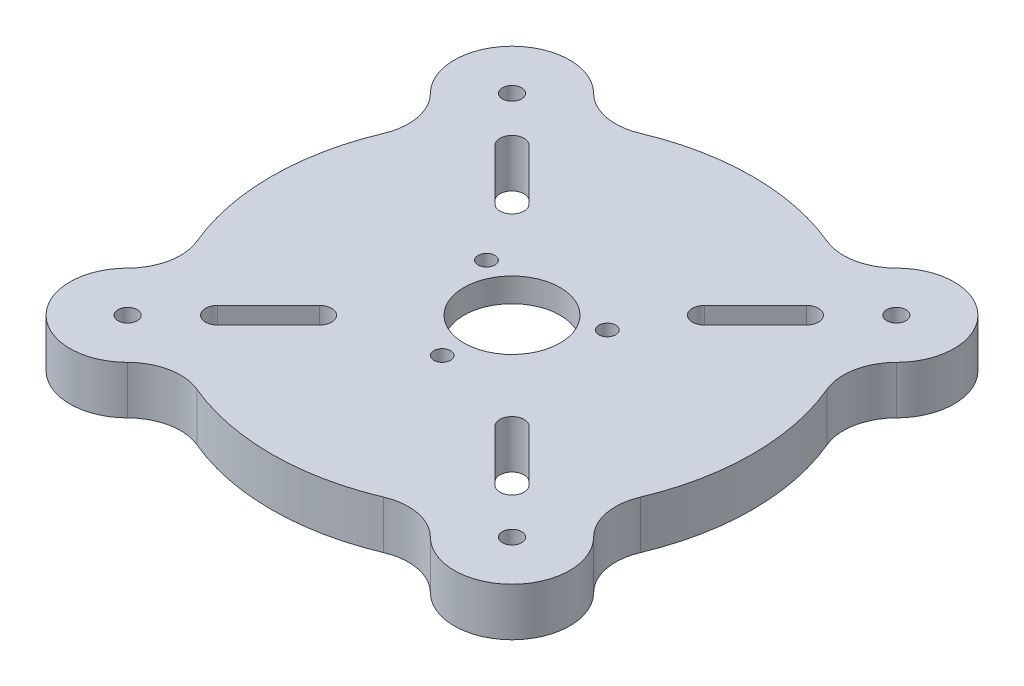
SolidWorks part; units mm, degrees
ref_plane "Front Plane" through (0, 0, 0) normal (0, 0, 1) x (1, 0, 0)
ref_plane "Top Plane" through (0, 0, 0) normal (0, 1, 0) x (1, 0, 0)
ref_plane "Right Plane" through (0, 0, 0) normal (1, 0, 0) x (0, 0, -1)
sketch "Sketch2" plane through (0, 0, 0) normal (0, 1, 0) x (1, 0, 0)
  line L0 (-39.9515, -39.9515) -> (39.9515, 39.9515) construction
  line L1 (-48.4368, -31.4663) -> (31.4663, 48.4368) construction
  line L2 (-31.4663, -48.4368) -> (48.4368, 31.4663) construction
  line L3 (0, 0) -> (0, 50) construction
  line L4 (39.9515, -39.9515) -> (-39.9515, 39.9515) construction
  line L5 (48.4368, -31.4663) -> (-31.4663, 48.4368) construction
  line L6 (31.4663, -48.4368) -> (-48.4368, 31.4663) construction
  line L7 (20, 20) -> (30.6066, 30.6066) construction
  line L8 (18.2322, 21.7678) -> (28.8388, 32.3744)
  line L9 (21.7678, 18.2322) -> (32.3744, 28.8388)
  line L10 (20, -20) -> (30.6066, -30.6066) construction
  line L11 (21.7678, -18.2322) -> (32.3744, -28.8388)
  line L12 (18.2322, -21.7678) -> (28.8388, -32.3744)
  line L13 (-20, -20) -> (-30.6066, -30.6066) construction
  line L14 (-18.2322, -21.7678) -> (-28.8388, -32.3744)
  line L15 (-21.7678, -18.2322) -> (-32.3744, -28.8388)
  line L16 (-20, 20) -> (-30.6066, 30.6066) construction
  line L17 (-21.7678, 18.2322) -> (-32.3744, 28.8388)
  line L18 (-18.2322, 21.7678) -> (-28.8388, 32.3744)
  circle A0 centre (0, 0) radius 50
  arc A1 (-48.4368, -31.4663) -> (-31.4663, -48.4368) centre (-39.9515, -39.9515) ccw construction
  arc A2 (48.4368, 31.4663) -> (31.4663, 48.4368) centre (39.9515, 39.9515) ccw construction
  arc A3 (48.4368, -31.4663) -> (31.4663, -48.4368) centre (39.9515, -39.9515) cw construction
  arc A4 (-48.4368, 31.4663) -> (-31.4663, 48.4368) centre (-39.9515, 39.9515) cw construction
  arc A5 (19.4135, 46.0773) -> (31.4663, 48.4368) centre (23.6858, 56.2173) ccw
  arc A6 (48.4368, 31.4663) -> (46.0773, 19.4135) centre (56.2173, 23.6858) ccw
  arc A7 (18.2322, 21.7678) -> (21.7678, 18.2322) centre (20, 20) ccw
  arc A8 (32.3744, 28.8388) -> (28.8388, 32.3744) centre (30.6066, 30.6066) ccw
  circle A9 centre (39.9515, 39.9515) radius 2
  arc A10 (31.4663, 48.4368) -> (48.4368, 31.4663) centre (39.9515, 39.9515) cw
  arc A11 (46.0773, -19.4135) -> (48.4368, -31.4663) centre (56.2173, -23.6858) ccw
  arc A12 (48.4368, -31.4663) -> (31.4663, -48.4368) centre (39.9515, -39.9515) cw
  arc A13 (31.4663, -48.4368) -> (19.4135, -46.0773) centre (23.6858, -56.2173) ccw
  arc A14 (-19.4135, -46.0773) -> (-31.4663, -48.4368) centre (-23.6858, -56.2173) ccw
  arc A15 (-31.4663, -48.4368) -> (-48.4368, -31.4663) centre (-39.9515, -39.9515) cw
  arc A16 (-48.4368, -31.4663) -> (-46.0773, -19.4135) centre (-56.2173, -23.6858) ccw
  arc A17 (-46.0773, 19.4135) -> (-48.4368, 31.4663) centre (-56.2173, 23.6858) ccw
  arc A18 (-48.4368, 31.4663) -> (-31.4663, 48.4368) centre (-39.9515, 39.9515) cw
  arc A19 (-31.4663, 48.4368) -> (-19.4135, 46.0773) centre (-23.6858, 56.2173) ccw
  circle A20 centre (39.9515, -39.9515) radius 2
  arc A21 (21.7678, -18.2322) -> (18.2322, -21.7678) centre (20, -20) ccw
  arc A22 (28.8388, -32.3744) -> (32.3744, -28.8388) centre (30.6066, -30.6066) ccw
  circle A23 centre (-39.9515, -39.9515) radius 2
  arc A24 (-18.2322, -21.7678) -> (-21.7678, -18.2322) centre (-20, -20) ccw
  arc A25 (-32.3744, -28.8388) -> (-28.8388, -32.3744) centre (-30.6066, -30.6066) ccw
  circle A26 centre (-39.9515, 39.9515) radius 2
  arc A27 (-21.7678, 18.2322) -> (-18.2322, 21.7678) centre (-20, 20) ccw
  arc A28 (-28.8388, 32.3744) -> (-32.3744, 28.8388) centre (-30.6066, 30.6066) ccw
  point P5 (0, 0)
  point P13 (0, 0)
  point P26 (25.3033, 25.3033)
  point P59 (0, 0)
  point P63 (25.3033, -25.3033)
  point P72 (-25.3033, -25.3033)
  point P81 (-25.3033, 25.3033)
  point P88 (0, 0)
  dimension "D1" = 100
  dimension "D2" = 12
  dimension "D5" = 2.5
  dimension "D8" = 4
  dimension "D3" = 113
  dimension "D4" = 45
  dimension "D6" = 15
  dimension "D7" = 20
  dimension "D11" = 18.2322
  dimension "D12" = 19.4135
  dimension "D13" = 18.2322
  dimension "D14" = 19.4135
  dimension "D9" = 4
  dimension "D10" = 4
extrude "Boss-Extrude2" add sketch "Sketch2" along normal blind 10 contours A19 A18 A17 A0 A26 | A16 A15 A14 A0 A23 | A0 A28 L18 A27 L17 A25 L15 A24 L14 A22 L12 A21 L11 A8 L9 A7 L8 | A13 A12 A11 A0 A20 | A10 A5 A0 A6 A9 region at (0, 0, 0) region at (35.6807, 0, -35.6807) region at (44.9674, 0, 25.8881) region at (-35.6807, 0, -35.6807) region at (-25.8881, 0, 44.9674)
sketch "Sketch3" plane through (0, 0, 0) normal (0, -1, 0) x (1, 0, 0)
  circle A0 centre (0, 0) radius 21.25
  circle A1 centre (0, 14.5) radius 1.75
  circle A2 centre (12.5574, -7.25) radius 1.75
  circle A3 centre (-12.5574, -7.25) radius 1.75
  point P12 (0, 0)
  dimension "D1" = 42.5
  dimension "D2" = 3.5
  dimension "D3" = 14.5
  dimension "D5" = 35.8794
  dimension "D6" = 48.4368
  dimension "D7" = 60.9942
  dimension "D4" = 3
extrude "Cut-Extrude8" cut sketch "Sketch3" against normal blind 5 contours A0 A3 A2 A1 region at (0, 0, 0)
extrude "Cut-Extrude9" cut sketch "Sketch3<9>" against normal through all contours A3 | A1 | A2
sketch "Sketch3<9>" plane through (0, 0, 0) normal (0, -1, 0) x (1, 0, 0) same geometry as "Sketch3"
sketch "Sketch5" plane through (0, 5, 0) normal (0, -1, 0) x (1, 0, 0)
  circle A0 centre (0, 0) radius 10
  dimension "D1" = 20
extrude "Cut-Extrude10" cut sketch "Sketch5" against normal through all contours A0
